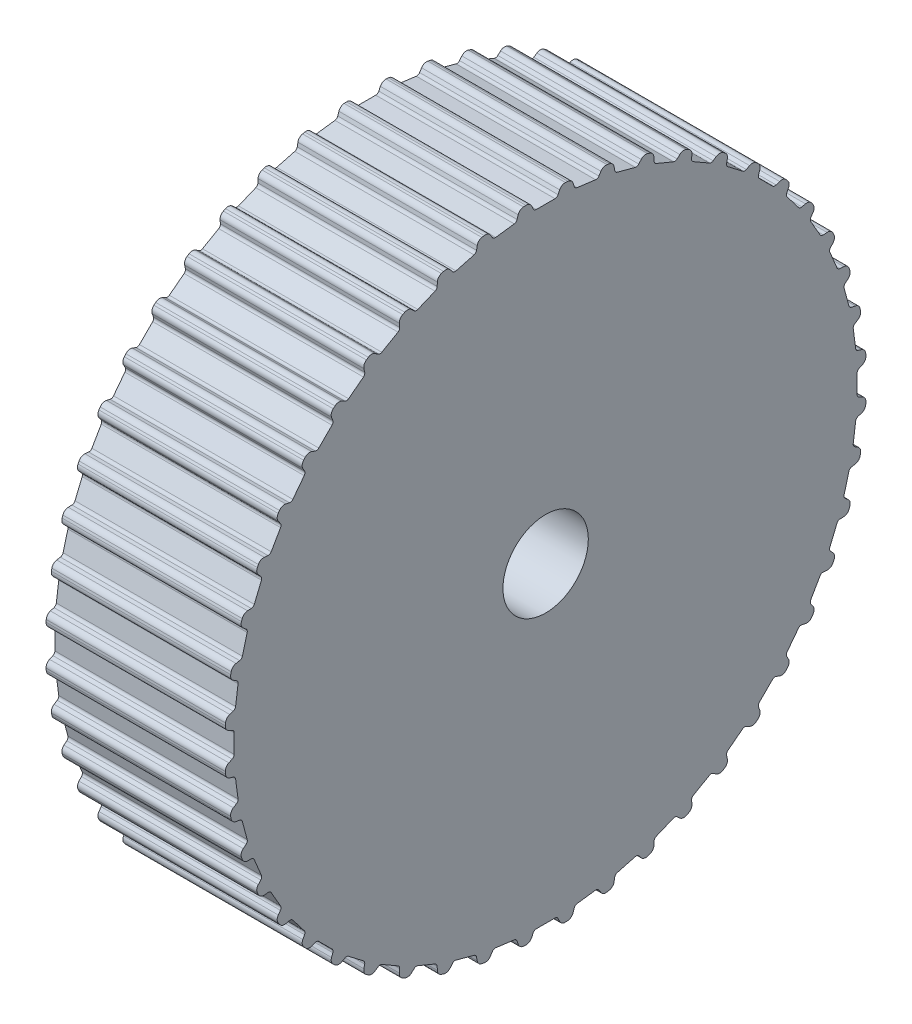
SolidWorks part; units mm, degrees
ref_plane "Front Plane" through (0, 0, 0) normal (0, 0, 1) x (1, 0, 0)
ref_plane "Top Plane" through (0, 0, 0) normal (0, 1, 0) x (1, 0, 0)
ref_plane "Right Plane" through (0, 0, 0) normal (1, 0, 0) x (0, 0, -1)
ref_plane "Plane1" through (0, 0, 0) normal (0, 0, -1) x (-1, 0, 0)
sketch "Sketch1" plane through (0, 0, 0) normal (0, 0, -1) x (-1, 0, 0)
  line L0 (-21, 37.585) -> (-21, 0)
  line L1 (-21, 0) -> (0, 0)
  line L2 (0, 0) -> (0, 37.585)
  line L3 (0, 37.585) -> (-21, 37.585)
  line L4 (-21, 0) -> (0, 0) construction
revolve "Revolve1" add sketch "Sketch1" angle 360 about L4 reverse direction yes
sketch "Sketch2" plane through (0, 0, 0) normal (-1, 0, 0) x (0, 0, 1)
  line L0 (3.0738, 37.4591) -> (3.4238, 36.3491)
  line L1 (3.4238, 36.3491) -> (6.1007, 35.9967)
  line L2 (6.1007, 35.9967) -> (6.7261, 36.9783)
  arc A0 (6.7261, 36.9783) -> (3.0738, 37.4591) centre (0, 0) ccw
extrude "Cut-Extrude1" cut sketch "Sketch2" against normal through all
sketch "Sketch3" plane through (0, 0, 0) normal (-1, 0, 0) x (0, 0, 1)
  line L0 (7.9369, 36.7374) -> (8.139, 35.5912)
  line L1 (8.139, 35.5912) -> (10.747, 34.8924)
  line L2 (10.747, 34.8924) -> (11.4951, 35.784)
  arc A0 (11.4951, 35.784) -> (7.9369, 36.7374) centre (0, 0) ccw
extrude "Cut-Extrude2" cut sketch "Sketch3" against normal through all
sketch "Sketch4" plane through (0, 0, 0) normal (-1, 0, 0) x (0, 0, 1)
  line L0 (12.6642, 35.3871) -> (12.715, 34.2244)
  line L1 (12.715, 34.2244) -> (15.2094, 33.1911)
  line L2 (15.2094, 33.1911) -> (16.0676, 33.9774)
  arc A0 (16.0676, 33.9774) -> (12.6642, 35.3871) centre (0, 0) ccw
extrude "Cut-Extrude3" cut sketch "Sketch4" against normal through all
sketch "Sketch5" plane through (0, 0, 0) normal (-1, 0, 0) x (0, 0, 1)
  line L0 (17.1748, 33.4314) -> (17.0734, 32.2719)
  line L1 (17.0734, 32.2719) -> (19.4116, 30.9219)
  line L2 (19.4116, 30.9219) -> (20.365, 31.5895)
  arc A0 (20.365, 31.5895) -> (17.1748, 33.4314) centre (0, 0) ccw
extrude "Cut-Extrude4" cut sketch "Sketch5" against normal through all
sketch "Sketch6" plane through (0, 0, 0) normal (-1, 0, 0) x (0, 0, 1)
  line L0 (21.3915, 30.9036) -> (21.1396, 29.7673)
  line L1 (21.1396, 29.7673) -> (23.2817, 28.1237)
  line L2 (23.2817, 28.1237) -> (24.3141, 28.6611)
  arc A0 (24.3141, 28.6611) -> (21.3915, 30.9036) centre (0, 0) ccw
extrude "Cut-Extrude5" cut sketch "Sketch6" against normal through all
sketch "Sketch7" plane through (0, 0, 0) normal (-1, 0, 0) x (0, 0, 1)
  line L0 (25.2423, 27.8471) -> (24.8442, 26.7534)
  line L1 (24.8442, 26.7534) -> (26.7534, 24.8442)
  line L2 (26.7534, 24.8442) -> (27.8471, 25.2423)
  arc A0 (27.8471, 25.2423) -> (25.2423, 27.8471) centre (0, 0) ccw
extrude "Cut-Extrude6" cut sketch "Sketch7" against normal through all
sketch "Sketch8" plane through (0, 0, 0) normal (-1, 0, 0) x (0, 0, 1)
  line L0 (28.6611, 24.3141) -> (28.1237, 23.2817)
  line L1 (28.1237, 23.2817) -> (29.7673, 21.1396)
  line L2 (29.7673, 21.1396) -> (30.9036, 21.3915)
  arc A0 (30.9036, 21.3915) -> (28.6611, 24.3141) centre (0, 0) ccw
extrude "Cut-Extrude7" cut sketch "Sketch8" against normal through all
sketch "Sketch9" plane through (0, 0, 0) normal (-1, 0, 0) x (0, 0, 1)
  line L0 (31.5895, 20.365) -> (30.9219, 19.4116)
  line L1 (30.9219, 19.4116) -> (32.2719, 17.0734)
  line L2 (32.2719, 17.0734) -> (33.4314, 17.1748)
  arc A0 (33.4314, 17.1748) -> (31.5895, 20.365) centre (0, 0) ccw
extrude "Cut-Extrude8" cut sketch "Sketch9" against normal through all
sketch "Sketch10" plane through (0, 0, 0) normal (-1, 0, 0) x (0, 0, 1)
  line L0 (33.9774, 16.0676) -> (33.1911, 15.2094)
  line L1 (33.1911, 15.2094) -> (34.2244, 12.715)
  line L2 (34.2244, 12.715) -> (35.3871, 12.6642)
  arc A0 (35.3871, 12.6642) -> (33.9774, 16.0676) centre (0, 0) ccw
extrude "Cut-Extrude9" cut sketch "Sketch10" against normal through all
sketch "Sketch11" plane through (0, 0, 0) normal (-1, 0, 0) x (0, 0, 1)
  line L0 (35.784, 11.4951) -> (34.8924, 10.747)
  line L1 (34.8924, 10.747) -> (35.5912, 8.139)
  line L2 (35.5912, 8.139) -> (36.7374, 7.9369)
  arc A0 (36.7374, 7.9369) -> (35.784, 11.4951) centre (0, 0) ccw
extrude "Cut-Extrude10" cut sketch "Sketch11" against normal through all
sketch "Sketch12" plane through (0, 0, 0) normal (-1, 0, 0) x (0, 0, 1)
  line L0 (36.9783, 6.7261) -> (35.9967, 6.1007)
  line L1 (35.9967, 6.1007) -> (36.3491, 3.4238)
  line L2 (36.3491, 3.4238) -> (37.4591, 3.0738)
  arc A0 (37.4591, 3.0738) -> (36.9783, 6.7261) centre (0, 0) ccw
extrude "Cut-Extrude11" cut sketch "Sketch12" against normal through all
sketch "Sketch13" plane through (0, 0, 0) normal (-1, 0, 0) x (0, 0, 1)
  line L0 (37.5398, 1.8419) -> (36.485, 1.35)
  line L1 (36.485, 1.35) -> (36.485, -1.35)
  line L2 (36.485, -1.35) -> (37.5398, -1.8419)
  arc A0 (37.5398, -1.8419) -> (37.5398, 1.8419) centre (0, 0) ccw
extrude "Cut-Extrude12" cut sketch "Sketch13" against normal through all
sketch "Sketch14" plane through (0, 0, 0) normal (-1, 0, 0) x (0, 0, 1)
  line L0 (37.4591, -3.0738) -> (36.3491, -3.4238)
  line L1 (36.3491, -3.4238) -> (35.9967, -6.1007)
  line L2 (35.9967, -6.1007) -> (36.9783, -6.7261)
  arc A0 (36.9783, -6.7261) -> (37.4591, -3.0738) centre (0, 0) ccw
extrude "Cut-Extrude13" cut sketch "Sketch14" against normal through all
sketch "Sketch15" plane through (0, 0, 0) normal (-1, 0, 0) x (0, 0, 1)
  line L0 (36.7374, -7.9369) -> (35.5912, -8.139)
  line L1 (35.5912, -8.139) -> (34.8924, -10.747)
  line L2 (34.8924, -10.747) -> (35.784, -11.4951)
  arc A0 (35.784, -11.4951) -> (36.7374, -7.9369) centre (0, 0) ccw
extrude "Cut-Extrude14" cut sketch "Sketch15" against normal through all
sketch "Sketch16" plane through (0, 0, 0) normal (-1, 0, 0) x (0, 0, 1)
  line L0 (35.3871, -12.6642) -> (34.2244, -12.715)
  line L1 (34.2244, -12.715) -> (33.1911, -15.2094)
  line L2 (33.1911, -15.2094) -> (33.9774, -16.0676)
  arc A0 (33.9774, -16.0676) -> (35.3871, -12.6642) centre (0, 0) ccw
extrude "Cut-Extrude15" cut sketch "Sketch16" against normal through all
sketch "Sketch17" plane through (0, 0, 0) normal (-1, 0, 0) x (0, 0, 1)
  line L0 (33.4314, -17.1748) -> (32.2719, -17.0734)
  line L1 (32.2719, -17.0734) -> (30.9219, -19.4116)
  line L2 (30.9219, -19.4116) -> (31.5895, -20.365)
  arc A0 (31.5895, -20.365) -> (33.4314, -17.1748) centre (0, 0) ccw
extrude "Cut-Extrude16" cut sketch "Sketch17" against normal through all
sketch "Sketch18" plane through (0, 0, 0) normal (-1, 0, 0) x (0, 0, 1)
  line L0 (30.9036, -21.3915) -> (29.7673, -21.1396)
  line L1 (29.7673, -21.1396) -> (28.1237, -23.2817)
  line L2 (28.1237, -23.2817) -> (28.6611, -24.3141)
  arc A0 (28.6611, -24.3141) -> (30.9036, -21.3915) centre (0, 0) ccw
extrude "Cut-Extrude17" cut sketch "Sketch18" against normal through all
sketch "Sketch19" plane through (0, 0, 0) normal (-1, 0, 0) x (0, 0, 1)
  line L0 (27.8471, -25.2423) -> (26.7534, -24.8442)
  line L1 (26.7534, -24.8442) -> (24.8442, -26.7534)
  line L2 (24.8442, -26.7534) -> (25.2423, -27.8471)
  arc A0 (25.2423, -27.8471) -> (27.8471, -25.2423) centre (0, 0) ccw
extrude "Cut-Extrude18" cut sketch "Sketch19" against normal through all
sketch "Sketch20" plane through (0, 0, 0) normal (-1, 0, 0) x (0, 0, 1)
  line L0 (24.3141, -28.6611) -> (23.2817, -28.1237)
  line L1 (23.2817, -28.1237) -> (21.1396, -29.7673)
  line L2 (21.1396, -29.7673) -> (21.3915, -30.9036)
  arc A0 (21.3915, -30.9036) -> (24.3141, -28.6611) centre (0, 0) ccw
extrude "Cut-Extrude19" cut sketch "Sketch20" against normal through all
sketch "Sketch21" plane through (0, 0, 0) normal (-1, 0, 0) x (0, 0, 1)
  line L0 (20.365, -31.5895) -> (19.4116, -30.9219)
  line L1 (19.4116, -30.9219) -> (17.0734, -32.2719)
  line L2 (17.0734, -32.2719) -> (17.1748, -33.4314)
  arc A0 (17.1748, -33.4314) -> (20.365, -31.5895) centre (0, 0) ccw
extrude "Cut-Extrude20" cut sketch "Sketch21" against normal through all
sketch "Sketch22" plane through (0, 0, 0) normal (-1, 0, 0) x (0, 0, 1)
  line L0 (16.0676, -33.9774) -> (15.2094, -33.1911)
  line L1 (15.2094, -33.1911) -> (12.715, -34.2244)
  line L2 (12.715, -34.2244) -> (12.6642, -35.3871)
  arc A0 (12.6642, -35.3871) -> (16.0676, -33.9774) centre (0, 0) ccw
extrude "Cut-Extrude21" cut sketch "Sketch22" against normal through all
sketch "Sketch23" plane through (0, 0, 0) normal (-1, 0, 0) x (0, 0, 1)
  line L0 (11.4951, -35.784) -> (10.747, -34.8924)
  line L1 (10.747, -34.8924) -> (8.139, -35.5912)
  line L2 (8.139, -35.5912) -> (7.9369, -36.7374)
  arc A0 (7.9369, -36.7374) -> (11.4951, -35.784) centre (0, 0) ccw
extrude "Cut-Extrude22" cut sketch "Sketch23" against normal through all
sketch "Sketch24" plane through (0, 0, 0) normal (-1, 0, 0) x (0, 0, 1)
  line L0 (6.7261, -36.9783) -> (6.1007, -35.9967)
  line L1 (6.1007, -35.9967) -> (3.4238, -36.3491)
  line L2 (3.4238, -36.3491) -> (3.0738, -37.4591)
  arc A0 (3.0738, -37.4591) -> (6.7261, -36.9783) centre (0, 0) ccw
extrude "Cut-Extrude23" cut sketch "Sketch24" against normal through all
sketch "Sketch25" plane through (0, 0, 0) normal (-1, 0, 0) x (0, 0, 1)
  line L0 (1.8419, -37.5398) -> (1.35, -36.485)
  line L1 (1.35, -36.485) -> (-1.35, -36.485)
  line L2 (-1.35, -36.485) -> (-1.8419, -37.5398)
  arc A0 (-1.8419, -37.5398) -> (1.8419, -37.5398) centre (0, 0) ccw
extrude "Cut-Extrude24" cut sketch "Sketch25" against normal through all
sketch "Sketch26" plane through (0, 0, 0) normal (-1, 0, 0) x (0, 0, 1)
  line L0 (-3.0738, -37.4591) -> (-3.4238, -36.3491)
  line L1 (-3.4238, -36.3491) -> (-6.1007, -35.9967)
  line L2 (-6.1007, -35.9967) -> (-6.7261, -36.9783)
  arc A0 (-6.7261, -36.9783) -> (-3.0738, -37.4591) centre (0, 0) ccw
extrude "Cut-Extrude25" cut sketch "Sketch26" against normal through all
sketch "Sketch27" plane through (0, 0, 0) normal (-1, 0, 0) x (0, 0, 1)
  line L0 (-7.9369, -36.7374) -> (-8.139, -35.5912)
  line L1 (-8.139, -35.5912) -> (-10.747, -34.8924)
  line L2 (-10.747, -34.8924) -> (-11.4951, -35.784)
  arc A0 (-11.4951, -35.784) -> (-7.9369, -36.7374) centre (0, 0) ccw
extrude "Cut-Extrude26" cut sketch "Sketch27" against normal through all
sketch "Sketch28" plane through (0, 0, 0) normal (-1, 0, 0) x (0, 0, 1)
  line L0 (-12.6642, -35.3871) -> (-12.715, -34.2244)
  line L1 (-12.715, -34.2244) -> (-15.2094, -33.1911)
  line L2 (-15.2094, -33.1911) -> (-16.0676, -33.9774)
  arc A0 (-16.0676, -33.9774) -> (-12.6642, -35.3871) centre (0, 0) ccw
extrude "Cut-Extrude27" cut sketch "Sketch28" against normal through all
sketch "Sketch29" plane through (0, 0, 0) normal (-1, 0, 0) x (0, 0, 1)
  line L0 (-17.1748, -33.4314) -> (-17.0734, -32.2719)
  line L1 (-17.0734, -32.2719) -> (-19.4116, -30.9219)
  line L2 (-19.4116, -30.9219) -> (-20.365, -31.5895)
  arc A0 (-20.365, -31.5895) -> (-17.1748, -33.4314) centre (0, 0) ccw
extrude "Cut-Extrude28" cut sketch "Sketch29" against normal through all
sketch "Sketch30" plane through (0, 0, 0) normal (-1, 0, 0) x (0, 0, 1)
  line L0 (-21.3915, -30.9036) -> (-21.1396, -29.7673)
  line L1 (-21.1396, -29.7673) -> (-23.2817, -28.1237)
  line L2 (-23.2817, -28.1237) -> (-24.3141, -28.6611)
  arc A0 (-24.3141, -28.6611) -> (-21.3915, -30.9036) centre (0, 0) ccw
extrude "Cut-Extrude29" cut sketch "Sketch30" against normal through all
sketch "Sketch31" plane through (0, 0, 0) normal (-1, 0, 0) x (0, 0, 1)
  line L0 (-25.2423, -27.8471) -> (-24.8442, -26.7534)
  line L1 (-24.8442, -26.7534) -> (-26.7534, -24.8442)
  line L2 (-26.7534, -24.8442) -> (-27.8471, -25.2423)
  arc A0 (-27.8471, -25.2423) -> (-25.2423, -27.8471) centre (0, 0) ccw
extrude "Cut-Extrude30" cut sketch "Sketch31" against normal through all
sketch "Sketch32" plane through (0, 0, 0) normal (-1, 0, 0) x (0, 0, 1)
  line L0 (-28.6611, -24.3141) -> (-28.1237, -23.2817)
  line L1 (-28.1237, -23.2817) -> (-29.7673, -21.1396)
  line L2 (-29.7673, -21.1396) -> (-30.9036, -21.3915)
  arc A0 (-30.9036, -21.3915) -> (-28.6611, -24.3141) centre (0, 0) ccw
extrude "Cut-Extrude31" cut sketch "Sketch32" against normal through all
sketch "Sketch33" plane through (0, 0, 0) normal (-1, 0, 0) x (0, 0, 1)
  line L0 (-31.5895, -20.365) -> (-30.9219, -19.4116)
  line L1 (-30.9219, -19.4116) -> (-32.2719, -17.0734)
  line L2 (-32.2719, -17.0734) -> (-33.4314, -17.1748)
  arc A0 (-33.4314, -17.1748) -> (-31.5895, -20.365) centre (0, 0) ccw
extrude "Cut-Extrude32" cut sketch "Sketch33" against normal through all
sketch "Sketch34" plane through (0, 0, 0) normal (-1, 0, 0) x (0, 0, 1)
  line L0 (-33.9774, -16.0676) -> (-33.1911, -15.2094)
  line L1 (-33.1911, -15.2094) -> (-34.2244, -12.715)
  line L2 (-34.2244, -12.715) -> (-35.3871, -12.6642)
  arc A0 (-35.3871, -12.6642) -> (-33.9774, -16.0676) centre (0, 0) ccw
extrude "Cut-Extrude33" cut sketch "Sketch34" against normal through all
sketch "Sketch35" plane through (0, 0, 0) normal (-1, 0, 0) x (0, 0, 1)
  line L0 (-35.784, -11.4951) -> (-34.8924, -10.747)
  line L1 (-34.8924, -10.747) -> (-35.5912, -8.139)
  line L2 (-35.5912, -8.139) -> (-36.7374, -7.9369)
  arc A0 (-36.7374, -7.9369) -> (-35.784, -11.4951) centre (0, 0) ccw
extrude "Cut-Extrude34" cut sketch "Sketch35" against normal through all
sketch "Sketch36" plane through (0, 0, 0) normal (-1, 0, 0) x (0, 0, 1)
  line L0 (-36.9783, -6.7261) -> (-35.9967, -6.1007)
  line L1 (-35.9967, -6.1007) -> (-36.3491, -3.4238)
  line L2 (-36.3491, -3.4238) -> (-37.4591, -3.0738)
  arc A0 (-37.4591, -3.0738) -> (-36.9783, -6.7261) centre (0, 0) ccw
extrude "Cut-Extrude35" cut sketch "Sketch36" against normal through all
sketch "Sketch37" plane through (0, 0, 0) normal (-1, 0, 0) x (0, 0, 1)
  line L0 (-37.5398, -1.8419) -> (-36.485, -1.35)
  line L1 (-36.485, -1.35) -> (-36.485, 1.35)
  line L2 (-36.485, 1.35) -> (-37.5398, 1.8419)
  arc A0 (-37.5398, 1.8419) -> (-37.5398, -1.8419) centre (0, 0) ccw
extrude "Cut-Extrude36" cut sketch "Sketch37" against normal through all
sketch "Sketch38" plane through (0, 0, 0) normal (-1, 0, 0) x (0, 0, 1)
  line L0 (-37.4591, 3.0738) -> (-36.3491, 3.4238)
  line L1 (-36.3491, 3.4238) -> (-35.9967, 6.1007)
  line L2 (-35.9967, 6.1007) -> (-36.9783, 6.7261)
  arc A0 (-36.9783, 6.7261) -> (-37.4591, 3.0738) centre (0, 0) ccw
extrude "Cut-Extrude37" cut sketch "Sketch38" against normal through all
sketch "Sketch39" plane through (0, 0, 0) normal (-1, 0, 0) x (0, 0, 1)
  line L0 (-36.7374, 7.9369) -> (-35.5912, 8.139)
  line L1 (-35.5912, 8.139) -> (-34.8924, 10.747)
  line L2 (-34.8924, 10.747) -> (-35.784, 11.4951)
  arc A0 (-35.784, 11.4951) -> (-36.7374, 7.9369) centre (0, 0) ccw
extrude "Cut-Extrude38" cut sketch "Sketch39" against normal through all
sketch "Sketch40" plane through (0, 0, 0) normal (-1, 0, 0) x (0, 0, 1)
  line L0 (-35.3871, 12.6642) -> (-34.2244, 12.715)
  line L1 (-34.2244, 12.715) -> (-33.1911, 15.2094)
  line L2 (-33.1911, 15.2094) -> (-33.9774, 16.0676)
  arc A0 (-33.9774, 16.0676) -> (-35.3871, 12.6642) centre (0, 0) ccw
extrude "Cut-Extrude39" cut sketch "Sketch40" against normal through all
sketch "Sketch41" plane through (0, 0, 0) normal (-1, 0, 0) x (0, 0, 1)
  line L0 (-33.4314, 17.1748) -> (-32.2719, 17.0734)
  line L1 (-32.2719, 17.0734) -> (-30.9219, 19.4116)
  line L2 (-30.9219, 19.4116) -> (-31.5895, 20.365)
  arc A0 (-31.5895, 20.365) -> (-33.4314, 17.1748) centre (0, 0) ccw
extrude "Cut-Extrude40" cut sketch "Sketch41" against normal through all
sketch "Sketch42" plane through (0, 0, 0) normal (-1, 0, 0) x (0, 0, 1)
  line L0 (-30.9036, 21.3915) -> (-29.7673, 21.1396)
  line L1 (-29.7673, 21.1396) -> (-28.1237, 23.2817)
  line L2 (-28.1237, 23.2817) -> (-28.6611, 24.3141)
  arc A0 (-28.6611, 24.3141) -> (-30.9036, 21.3915) centre (0, 0) ccw
extrude "Cut-Extrude41" cut sketch "Sketch42" against normal through all
sketch "Sketch43" plane through (0, 0, 0) normal (-1, 0, 0) x (0, 0, 1)
  line L0 (-27.8471, 25.2423) -> (-26.7534, 24.8442)
  line L1 (-26.7534, 24.8442) -> (-24.8442, 26.7534)
  line L2 (-24.8442, 26.7534) -> (-25.2423, 27.8471)
  arc A0 (-25.2423, 27.8471) -> (-27.8471, 25.2423) centre (0, 0) ccw
extrude "Cut-Extrude42" cut sketch "Sketch43" against normal through all
sketch "Sketch44" plane through (0, 0, 0) normal (-1, 0, 0) x (0, 0, 1)
  line L0 (-24.3141, 28.6611) -> (-23.2817, 28.1237)
  line L1 (-23.2817, 28.1237) -> (-21.1396, 29.7673)
  line L2 (-21.1396, 29.7673) -> (-21.3915, 30.9036)
  arc A0 (-21.3915, 30.9036) -> (-24.3141, 28.6611) centre (0, 0) ccw
extrude "Cut-Extrude43" cut sketch "Sketch44" against normal through all
sketch "Sketch45" plane through (0, 0, 0) normal (-1, 0, 0) x (0, 0, 1)
  line L0 (-20.365, 31.5895) -> (-19.4116, 30.9219)
  line L1 (-19.4116, 30.9219) -> (-17.0734, 32.2719)
  line L2 (-17.0734, 32.2719) -> (-17.1748, 33.4314)
  arc A0 (-17.1748, 33.4314) -> (-20.365, 31.5895) centre (0, 0) ccw
extrude "Cut-Extrude44" cut sketch "Sketch45" against normal through all
sketch "Sketch46" plane through (0, 0, 0) normal (-1, 0, 0) x (0, 0, 1)
  line L0 (-16.0676, 33.9774) -> (-15.2094, 33.1911)
  line L1 (-15.2094, 33.1911) -> (-12.715, 34.2244)
  line L2 (-12.715, 34.2244) -> (-12.6642, 35.3871)
  arc A0 (-12.6642, 35.3871) -> (-16.0676, 33.9774) centre (0, 0) ccw
extrude "Cut-Extrude45" cut sketch "Sketch46" against normal through all
sketch "Sketch47" plane through (0, 0, 0) normal (-1, 0, 0) x (0, 0, 1)
  line L0 (-11.4951, 35.784) -> (-10.747, 34.8924)
  line L1 (-10.747, 34.8924) -> (-8.139, 35.5912)
  line L2 (-8.139, 35.5912) -> (-7.9369, 36.7374)
  arc A0 (-7.9369, 36.7374) -> (-11.4951, 35.784) centre (0, 0) ccw
extrude "Cut-Extrude46" cut sketch "Sketch47" against normal through all
sketch "Sketch48" plane through (0, 0, 0) normal (-1, 0, 0) x (0, 0, 1)
  line L0 (-6.7261, 36.9783) -> (-6.1007, 35.9967)
  line L1 (-6.1007, 35.9967) -> (-3.4238, 36.3491)
  line L2 (-3.4238, 36.3491) -> (-3.0738, 37.4591)
  arc A0 (-3.0738, 37.4591) -> (-6.7261, 36.9783) centre (0, 0) ccw
extrude "Cut-Extrude47" cut sketch "Sketch48" against normal through all
sketch "Sketch49" plane through (0, 0, 0) normal (-1, 0, 0) x (0, 0, 1)
  line L0 (-1.8419, 37.5398) -> (-1.35, 36.485)
  line L1 (-1.35, 36.485) -> (1.35, 36.485)
  line L2 (1.35, 36.485) -> (1.8419, 37.5398)
  arc A0 (1.8419, 37.5398) -> (-1.8419, 37.5398) centre (0, 0) ccw
extrude "Cut-Extrude48" cut sketch "Sketch49" against normal through all
sketch "Sketch50" plane through (0, 0, 0) normal (0, 0, -1) x (-1, 0, 0)
  line L0 (-27, 25) -> (-27, 0)
  line L1 (-27, 0) -> (-21, 0)
  line L2 (-21, 0) -> (-21, 25)
  line L3 (-21, 25) -> (-27, 25)
  line L4 (-27, 0) -> (-21, 0) construction
revolve "Revolve2" add sketch "Sketch50" angle 360 about L4 reverse direction yes
hole_wizard "Ø8.0 (8) Diameter Hole1" positions "Sketch52" profile "Sketch51" hole size "Ø8.0" standard "ANSI Metric"
sketch "Sketch52" plane through (27, 0, 0) normal (1, 0, 0) x (0, 0, -1)
  point P0 (0, 0)
sketch "Sketch51" plane through (27, 0, 0) normal (0, 1, 0) x (0, 0, -1)
  line L0 (0, 0) -> (0, 27)
  line L1 (0, 27) -> (4, 27)
  line L2 (4, 27) -> (4, 0)
  line L5 (4, 0) -> (0, 0)
  line L11 (0, -6.35) -> (0, 107.95) construction
  dimension "Thru Hole Dia." = 8
  dimension "Thru Hole Depth" = 27
fillet "Fillet1" radius 0.4 96 edges at (10.5, -19.4116, -30.9219) (10.5, 36.485, -1.35) (10.5, 17.0734, -32.2719) (10.5, 36.3491, 3.4238) (10.5, -32.2719, -17.0734) (10.5, 34.8924, 10.747) (10.5, -1.35, -36.485) (10.5, 35.5912, 8.139) (10.5, 30.9219, -19.4116) (10.5, 33.1911, 15.2094) (10.5, -35.5912, -8.139) (10.5, 34.2244, 12.715) (10.5, -26.7534, -24.8442) (10.5, 30.9219, 19.4116) (10.5, -10.747, -34.8924) (10.5, 32.2719, 17.0734) (10.5, 8.139, -35.5912) (10.5, 28.1237, 23.2817) (10.5, 24.8442, -26.7534) (10.5, 29.7673, 21.1396) (10.5, 34.8924, -10.747) (10.5, 24.8442, 26.7534) (10.5, -36.3491, -3.4238) (10.5, 26.7534, 24.8442) (10.5, -34.2244, -12.715) (10.5, 21.1396, 29.7673) (10.5, -29.7673, -21.1396) (10.5, 23.2817, 28.1237) (10.5, -23.2817, -28.1237) (10.5, 17.0734, 32.2719) (10.5, -15.2094, -33.1911) (10.5, 19.4116, 30.9219) (10.5, -6.1007, -35.9967) (10.5, 12.715, 34.2244) (10.5, 3.4238, -36.3491) (10.5, 15.2094, 33.1911) (10.5, 12.715, -34.2244) (10.5, 8.139, 35.5912) (10.5, 21.1396, -29.7673) (10.5, 10.747, 34.8924) (10.5, 28.1237, -23.2817) (10.5, 3.4238, 36.3491) (10.5, 33.1911, -15.2094) (10.5, 6.1007, 35.9967) (10.5, 35.9967, -6.1007) (10.5, -1.35, 36.485) (10.5, -35.9967, -6.1007) (10.5, 1.35, 36.485) (10.5, -34.8924, -10.747) (10.5, -6.1007, 35.9967) (10.5, -33.1911, -15.2094) (10.5, -3.4238, 36.3491) (10.5, -30.9219, -19.4116) (10.5, -10.747, 34.8924) (10.5, -28.1237, -23.2817) (10.5, -8.139, 35.5912) (10.5, -24.8442, -26.7534) (10.5, -15.2094, 33.1911) (10.5, -21.1396, -29.7673) (10.5, -12.715, 34.2244) (10.5, -17.0734, -32.2719) (10.5, -19.4116, 30.9219) (10.5, -12.715, -34.2244) (10.5, -17.0734, 32.2719) (10.5, -8.139, -35.5912) (10.5, -23.2817, 28.1237) (10.5, -3.4238, -36.3491) (10.5, -21.1396, 29.7673) (10.5, 1.35, -36.485) (10.5, -26.7534, 24.8442) (10.5, 6.1007, -35.9967) (10.5, -24.8442, 26.7534) (10.5, 10.747, -34.8924) (10.5, -29.7673, 21.1396) (10.5, 15.2094, -33.1911) (10.5, -28.1237, 23.2817) (10.5, 19.4116, -30.9219) (10.5, -32.2719, 17.0734) (10.5, 23.2817, -28.1237) (10.5, -30.9219, 19.4116) (10.5, 26.7534, -24.8442) (10.5, -34.2244, 12.715) (10.5, 29.7673, -21.1396) (10.5, -33.1911, 15.2094) (10.5, 32.2719, -17.0734) (10.5, -35.5912, 8.139) (10.5, 34.2244, -12.715) (10.5, -34.8924, 10.747) (10.5, 35.5912, -8.139) (10.5, -36.3491, 3.4238) (10.5, 36.3491, -3.4238) (10.5, -35.9967, 6.1007) (10.5, 36.485, 1.35) (10.5, -36.485, -1.35) (10.5, 35.9967, 6.1007) (10.5, -36.485, 1.35) tangent propagation no
fillet "Fillet2" radius 0.7 96 edges at (10.5, -20.365, -31.5895) (10.5, 36.9783, 6.7261) (10.5, 17.1748, -33.4314) (10.5, 37.4591, 3.0738) (10.5, -33.4314, -17.1748) (10.5, 35.784, 11.4951) (10.5, -1.8419, -37.5398) (10.5, 36.7374, 7.9369) (10.5, 31.5895, -20.365) (10.5, 33.9774, 16.0676) (10.5, -36.7374, -7.9369) (10.5, 35.3871, 12.6642) (10.5, -27.8471, -25.2423) (10.5, 31.5895, 20.365) (10.5, -11.4951, -35.784) (10.5, 33.4314, 17.1748) (10.5, 7.9369, -36.7374) (10.5, 28.6611, 24.3141) (10.5, 25.2423, -27.8471) (10.5, 30.9036, 21.3915) (10.5, 35.784, -11.4951) (10.5, 25.2423, 27.8471) (10.5, -37.4591, -3.0738) (10.5, 27.8471, 25.2423) (10.5, -35.3871, -12.6642) (10.5, 21.3915, 30.9036) (10.5, -30.9036, -21.3915) (10.5, 24.3141, 28.6611) (10.5, -24.3141, -28.6611) (10.5, 17.1748, 33.4314) (10.5, -16.0676, -33.9774) (10.5, 20.365, 31.5895) (10.5, -6.7261, -36.9783) (10.5, 12.6642, 35.3871) (10.5, 3.0738, -37.4591) (10.5, 16.0676, 33.9774) (10.5, 12.6642, -35.3871) (10.5, 7.9369, 36.7374) (10.5, 21.3915, -30.9036) (10.5, 11.4951, 35.784) (10.5, 28.6611, -24.3141) (10.5, 3.0738, 37.4591) (10.5, 33.9774, -16.0676) (10.5, 6.7261, 36.9783) (10.5, 36.9783, -6.7261) (10.5, -1.8419, 37.5398) (10.5, -36.9783, -6.7261) (10.5, 1.8419, 37.5398) (10.5, -35.784, -11.4951) (10.5, -6.7261, 36.9783) (10.5, -33.9774, -16.0676) (10.5, -3.0738, 37.4591) (10.5, -31.5895, -20.365) (10.5, -11.4951, 35.784) (10.5, -28.6611, -24.3141) (10.5, -7.9369, 36.7374) (10.5, -25.2423, -27.8471) (10.5, -16.0676, 33.9774) (10.5, -21.3915, -30.9036) (10.5, -12.6642, 35.3871) (10.5, -17.1748, -33.4314) (10.5, -20.365, 31.5895) (10.5, -12.6642, -35.3871) (10.5, -17.1748, 33.4314) (10.5, -7.9369, -36.7374) (10.5, -24.3141, 28.6611) (10.5, -3.0738, -37.4591) (10.5, -21.3915, 30.9036) (10.5, 1.8419, -37.5398) (10.5, -27.8471, 25.2423) (10.5, 6.7261, -36.9783) (10.5, -25.2423, 27.8471) (10.5, 11.4951, -35.784) (10.5, -30.9036, 21.3915) (10.5, 16.0676, -33.9774) (10.5, -28.6611, 24.3141) (10.5, 20.365, -31.5895) (10.5, -33.4314, 17.1748) (10.5, 24.3141, -28.6611) (10.5, -31.5895, 20.365) (10.5, 27.8471, -25.2423) (10.5, -35.3871, 12.6642) (10.5, 30.9036, -21.3915) (10.5, -33.9774, 16.0676) (10.5, 33.4314, -17.1748) (10.5, -36.7374, 7.9369) (10.5, 35.3871, -12.6642) (10.5, -35.784, 11.4951) (10.5, 36.7374, -7.9369) (10.5, -37.4591, 3.0738) (10.5, 37.4591, -3.0738) (10.5, -36.9783, 6.7261) (10.5, 37.5398, 1.8419) (10.5, -37.5398, -1.8419) (10.5, -37.5398, 1.8419) (10.5, 37.5398, -1.8419) tangent propagation no
sketch "Sketch53" plane through (27, 0, 0) normal (1, 0, 0) x (0, 0, -1)
  circle A0 centre (0, 0) radius 5
  dimension "D1" = 10
extrude "Cut-Extrude49" cut sketch "Sketch53" against normal through all
sketch "Sketch54" plane through (27, 0, 0) normal (1, 0, 0) x (0, 0, -1)
  circle A1 centre (0, 0) radius 25
  circle A2 centre (0, 0) radius 25
  dimension "D1" = 0
extrude "Cut-Extrude50" cut sketch "Sketch54" against normal up to surface (6 mm away) up to face at (21, 0, -25)
